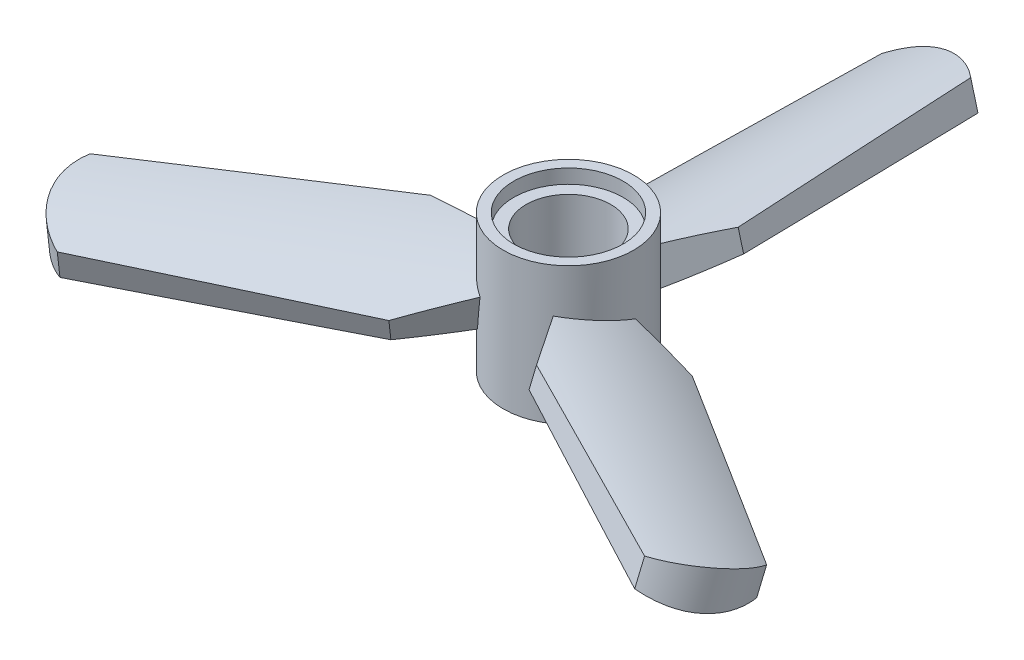
SolidWorks part; units mm, degrees
ref_plane "Front Plane" through (0, 0, 0) normal (0, 0, 1) x (1, 0, 0)
ref_plane "Top Plane" through (0, 0, 0) normal (0, 1, 0) x (1, 0, 0)
ref_plane "Right Plane" through (0, 0, 0) normal (1, 0, 0) x (0, 0, -1)
sketch "Sketch1" plane through (0, 0, 0) normal (0, 1, 0) x (1, 0, 0)
  circle A0 centre (0, 0) radius 3.7
  circle A1 centre (0, 0) radius 2.4
  dimension "D1" = 4.8
  dimension "D2" = 7.4
extrude "Hub" add sketch "Sketch1" along normal mid plane 7.8
sketch "Sketch2" plane through (0, 3.9, 0) normal (0, 1, 0) x (1, 0, 0)
  circle A2 centre (0, 0) radius 3.1
  circle A3 centre (0, 0) radius 3.1
  dimension "D1" = 0.7
extrude "Rim Cut " cut sketch "Sketch2" against normal blind 0.8
mirror "Mirror1" about plane through (0, 0, 0) normal (0, 1, 0) of "Rim Cut "
sketch "Sketch3" plane through (0, 0, 0) normal (0, 1, 0) x (1, 0, 0)
  line L0 (0, 0) -> (0, 12.5589) construction
  line L1 (2, 3.7) -> (-2, 3.7) construction
  line L2 (-2, 3.7) -> (-3.35, 6.55)
  line L3 (-3.35, 6.55) -> (-2.625, 20.5)
  line L4 (-2.625, 20.5) -> (2.625, 20.5) construction
  line L5 (3.35, 6.55) -> (2.625, 20.5)
  line L6 (2, 3.7) -> (3.35, 6.55)
  line L7 (1.5263, 2.7) -> (-1.5263, 2.7)
  line L8 (-2, 3.7) -> (-1.5263, 2.7)
  line L9 (2, 3.7) -> (1.5263, 2.7)
  circle A0 centre (0, 0) radius 3.7 construction
  arc A1 (-2.625, 20.5) -> (2.625, 20.5) centre (0, 17.5547) cw
  point P11 (0, 20.5)
  point P13 (0, 3.7)
  point P14 (-1.5211, 2.7877)
  point P15 (1.4236, 2.4831)
  point P17 (0, 2.7)
  dimension "D1" = 4
  dimension "D2" = 2.85
  dimension "D3" = 6.7
  dimension "D4" = 5.25
  dimension "D5" = 16.8
  dimension "D6" = 1
  dimension "D7" = 1
extrude "Blade" add sketch "Sketch3" along normal mid plane 2.2 separate body
sketch "Sketch4" plane through (0, 0, 0) normal (0, 0, 1) x (1, 0, 0)
  line L1 (3.35, 1.1) -> (-3.35, 1.1)
  line L4 (3.35, 1.1) -> (2.625, 1.1) construction
  line L5 (-2.625, 1.1) -> (-3.35, 1.1) construction
  line L6 (-3.35, 1.1) -> (-3.35, -1.1) construction
  line L7 (3.35, 1.1) -> (3.35, -1.1) construction
  line L8 (3.35, 0.6) -> (3.35, 1.1)
  line L9 (-3.35, 0.6) -> (-3.35, 1.1)
  line L10 (0, 0) -> (2.5357, 0) construction
  line L11 (-3.35, -0.6) -> (-3.35, -1.1)
  line L12 (3.35, -0.6) -> (3.35, -1.1)
  line L13 (3.35, -1.1) -> (-3.35, -1.1)
  arc A0 (3.35, 0.6) -> (-3.35, 0.6) centre (0, -10.3725) ccw
  arc A1 (3.35, -0.6) -> (-3.35, -0.6) centre (0, 10.3725) cw
  dimension "D1" = 0.5
extrude "Blade Curve" cut sketch "Sketch4" against normal through all contours A0 L8 L1 | A0 L1 L9 | L13 A1 L11 | L12 A1 L13 region at (2.5162, 0.9506, 0) region at (-2.5162, 0.9506, 0) region at (-2.5162, -0.9506, 0) region at (2.5162, -0.9506, 0)
ref_axis "Axis1" through (0, 0, -22.76) along (0, 0, 1)
move or copy body "Body-Move/Copy1" bodies to move or copy 105 copy no rotation origin (0, 0, 0) rotation axis (0, 0, 1) rotation angle 15
pattern_circular "CirPattern1" count 3 over 360 about axis through (0, 3.9, 0) along (0, -1, 0) of bodies 106
combine bodies "Combine1" bodies to combine 108 103 106 107
